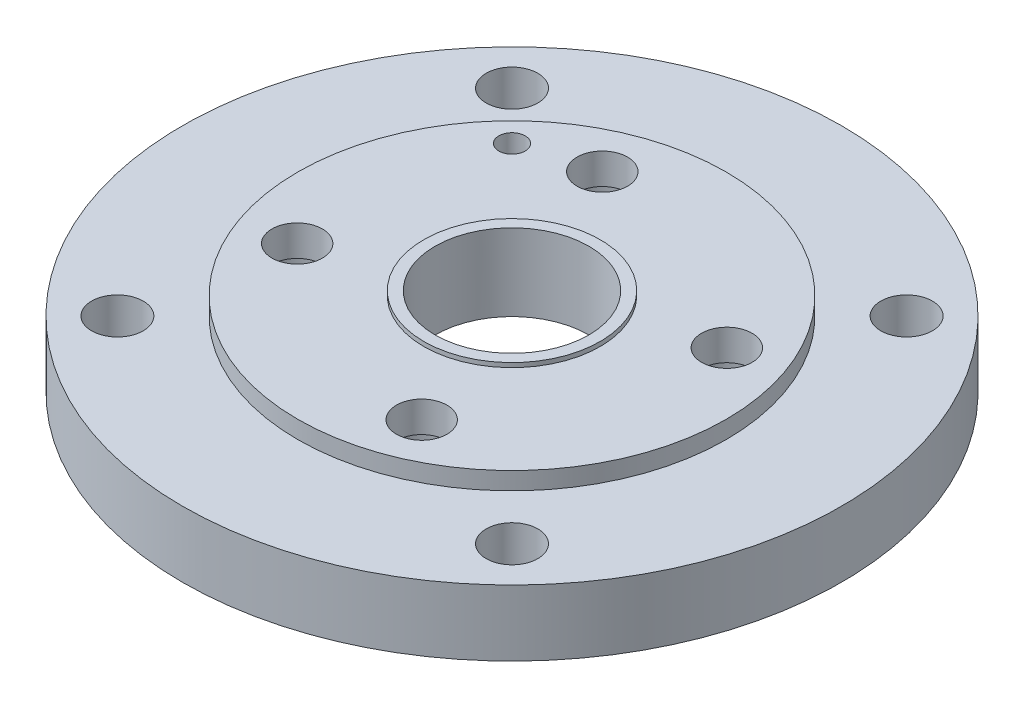
SolidWorks part; units mm, degrees
ref_plane "Front Plane" through (0, 0, 0) normal (0, 0, 1) x (1, 0, 0)
ref_plane "Top Plane" through (0, 0, 0) normal (0, 1, 0) x (1, 0, 0)
ref_plane "Right Plane" through (0, 0, 0) normal (1, 0, 0) x (0, 0, -1)
sketch "Sketch1" plane through (0, 0, 0) normal (0, 1, 0) x (1, 0, 0)
  line L0 (-28.3381, 69.4403) -> (0, 0) construction
  line L1 (0, 0) -> (-60, 60) construction
  line L2 (-60, 60) -> (-89.8026, 89.8026) construction
  circle A0 centre (0, 0) radius 150
  circle A1 centre (0, 0) radius 127 construction
  circle A2 centre (0, 0) radius 75 construction
  circle A3 centre (-28.3381, 69.4403) radius 17.5
  circle A4 centre (-28.3381, 69.4403) radius 11.5
  circle A5 centre (-69.4403, -28.3381) radius 17.5
  circle A6 centre (-69.4403, -28.3381) radius 11.5
  circle A7 centre (28.3381, -69.4403) radius 17.5
  circle A8 centre (28.3381, -69.4403) radius 11.5
  circle A9 centre (69.4403, 28.3381) radius 17.5
  circle A10 centre (69.4403, 28.3381) radius 11.5
  circle A11 centre (-60, 60) radius 6
  circle A12 centre (-89.8026, 89.8026) radius 11.75
  circle A13 centre (89.8026, 89.8026) radius 11.75
  circle A14 centre (89.8026, -89.8026) radius 11.75
  circle A15 centre (-89.8026, -89.8026) radius 11.75
  circle A16 centre (0, 0) radius 97.5
  circle A17 centre (0, 0) radius 35
  circle A18 centre (0, 0) radius 40.15
  point P20 (0, 0)
  point P31 (0, 0)
  dimension "D1" = 300
  dimension "D2" = 254
  dimension "D3" = 150
  dimension "D5" = 35
  dimension "D6" = 23
  dimension "D8" = 12
  dimension "D11" = 23.5
  dimension "D13" = 195
  dimension "D14" = 80.3
  dimension "D15" = 70
  dimension "D4" = 22.2
  dimension "D9" = 60
  dimension "D10" = 60
  dimension "D7" = 4
  dimension "D12" = 4
extrude "Boss-Extrude1" add sketch "Sketch1" along normal blind 30 contours A0 A16 A15 A14 A13 A12 region at (-145.7574, 0, 0)
extrude "Boss-Extrude2" add sketch "Sketch1<3>" along normal blind 38 contours A16 A18 A3 A5 A7 A9 A11 region at (-94.7423, 0, 0)
sketch "Sketch1<3>" plane through (0, 0, 0) normal (0, 1, 0) x (1, 0, 0) same geometry as "Sketch1"
extrude "Boss-Extrude3" add sketch "Sketch1<4>" along normal blind 40 contours A18 A17 region at (-39.0144, 0, 0)
sketch "Sketch1<4>" plane through (0, 0, 0) normal (0, 1, 0) x (1, 0, 0) same geometry as "Sketch1"
extrude "Boss-Extrude4" add sketch "Sketch1<5>" against normal blind 14 from surface contours A3 A4 | A9 A10 | A7 A8 | A5 A6 region at (-45.3431, 0, -69.4403) region at (-86.4453, 0, 28.3381) region at (11.333, 0, 69.4403) region at (52.4353, 0, -28.3381) starting at face at (0, 38, 40.15)
sketch "Sketch1<5>" plane through (0, 0, 0) normal (0, 1, 0) x (1, 0, 0) same geometry as "Sketch1"
sketch "Sketch2" plane through (0, 0, 0) normal (0, -1, 0) x (1, 0, 0)
  circle A0 centre (0, 0) radius 43.5
  dimension "D1" = 87
extrude "Cut-Extrude1" cut sketch "Sketch2" against normal blind 5 and the other way through all
